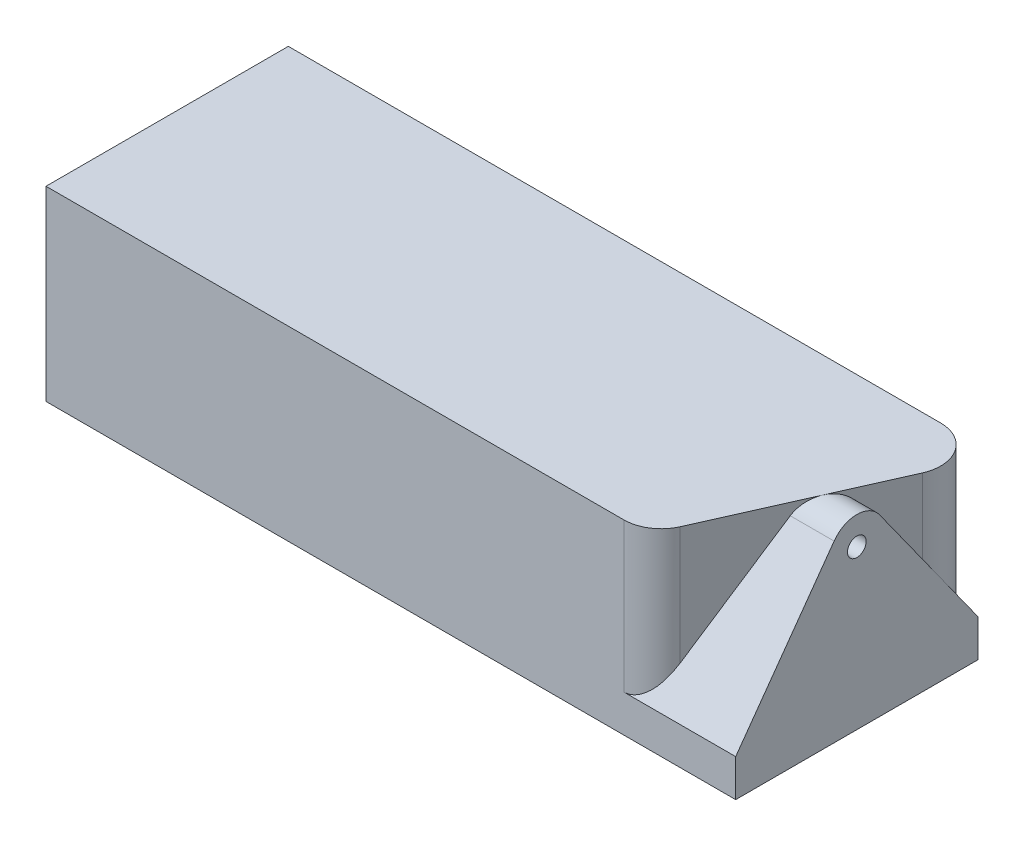
SolidWorks part; units mm, degrees
ref_plane "Front Plane" through (0, 0, 0) normal (0, 0, 1) x (1, 0, 0)
ref_plane "Top Plane" through (0, 0, 0) normal (0, 1, 0) x (1, 0, 0)
ref_plane "Right Plane" through (0, 0, 0) normal (1, 0, 0) x (0, 0, -1)
sketch "Sketch1" plane through (0, 0, 0) normal (0, 1, 0) x (1, 0, 0)
  line L0 (0, -10.3187) -> (0, 10.3187)
  line L1 (0, 10.3187) -> (55.5625, 10.3188)
  line L2 (58.4639, 5.8543) -> (52.1139, -8.4332)
  line L3 (49.2125, -10.3187) -> (0, -10.3187)
  arc A0 (55.5625, 10.3188) -> (58.4639, 5.8543) centre (55.5625, 7.1437) cw
  arc A1 (52.1139, -8.4332) -> (49.2125, -10.3187) centre (49.2125, -7.1437) cw
  point P3 (0, 0)
  point P4 (0, 0)
  point P11 (46.0375, 10.3187)
  point P12 (51.5536, -6.0549)
  point P13 (51.3212, -6.5632)
  dimension "D4" = 3.175
  dimension "D1" = 20.6375
  dimension "D2" = 46.0375
  dimension "D3" = 9.525
  dimension "D5" = 6.35
sketch "Sketch2" plane through (0, 0, 0) normal (0, 0, 1) x (1, 0, 0)
  line L0 (0, 0) -> (0, 3.175)
  line L1 (0, 3.175) -> (1.5875, 3.175)
  line L2 (1.5875, 3.175) -> (1.5875, 15.875)
  line L3 (1.5875, 15.875) -> (3.9688, 15.875)
  line L4 (3.9688, 15.875) -> (3.9688, 3.175)
  line L5 (3.9688, 3.175) -> (7.1438, 3.175)
  line L6 (7.1438, 3.175) -> (7.1438, 15.875)
  line L7 (7.1438, 15.875) -> (9.525, 15.875)
  line L8 (9.525, 15.875) -> (9.525, 3.175)
  line L9 (9.525, 3.175) -> (58.7375, 3.175)
  line L10 (58.7375, 3.175) -> (58.7375, 0)
  line L11 (58.7375, 0) -> (0, 0)
  dimension "D1" = 3.175
  dimension "D2" = 1.5875
  dimension "D3" = 12.7
  dimension "D4" = 2.3813
  dimension "D5" = 3.175
  dimension "D6" = 58.7375
sketch "Sketch3" plane through (0, 0, 0) normal (1, 0, 0) x (0, 0, -1)
  line L0 (10.3187, 0) -> (-10.3187, 0)
  line L2 (-10.3187, 0) -> (-10.3187, 3.175)
  line L3 (-10.3187, 3.175) -> (-1.936, 14.8802)
  line L4 (1.936, 14.8802) -> (10.3187, 3.175)
  line L5 (10.3187, 3.175) -> (10.3187, 0)
  arc A0 (-1.936, 14.8802) -> (1.936, 14.8802) centre (0, 13.4937) cw
  circle A1 centre (0, 13.4937) radius 0.7937
  point P3 (0, 0)
  point P4 (0, 0)
  point P11 (0, 0)
  point P12 (0, 0)
  point P13 (0, 0)
  dimension "D4" = 2.3813
  dimension "D1" = 20.6375
  dimension "D5" = 1.5875
  dimension "D2" = 3.175
  dimension "D3" = 10.3187
extrude "Boss-Extrude1" add sketch "Sketch1" along normal blind 15.875
extrude "Boss-Extrude2" add sketch "Sketch2" along normal blind 10.3187 and the other way blind 10.3187 separate body
extrude "Boss-Extrude3" add sketch "Sketch3" along normal blind 58.7375
equation "\"D6@Sketch2\"= \"D2@Sketch1\" + \"D3@Sketch1\" + \"D4@Sketch1\""
equation "\"D1@Sketch3\" = \"D1@Sketch1\""
equation "\"D2@Sketch3\"= \"D1@Sketch2\""
equation "\"D1@Boss-Extrude1\"= \"D1@Sketch2\" + \"D3@Sketch2\""
equation "\"D1@Boss-Extrude2\"= \"D1@Sketch1\" / 2"
equation "\"D2@Boss-Extrude2\" = \"D1@Boss-Extrude2\""
equation "\"D1@Boss-Extrude3\"= \"D2@Sketch1\" + \"D3@Sketch1\" + \"D4@Sketch1\""
